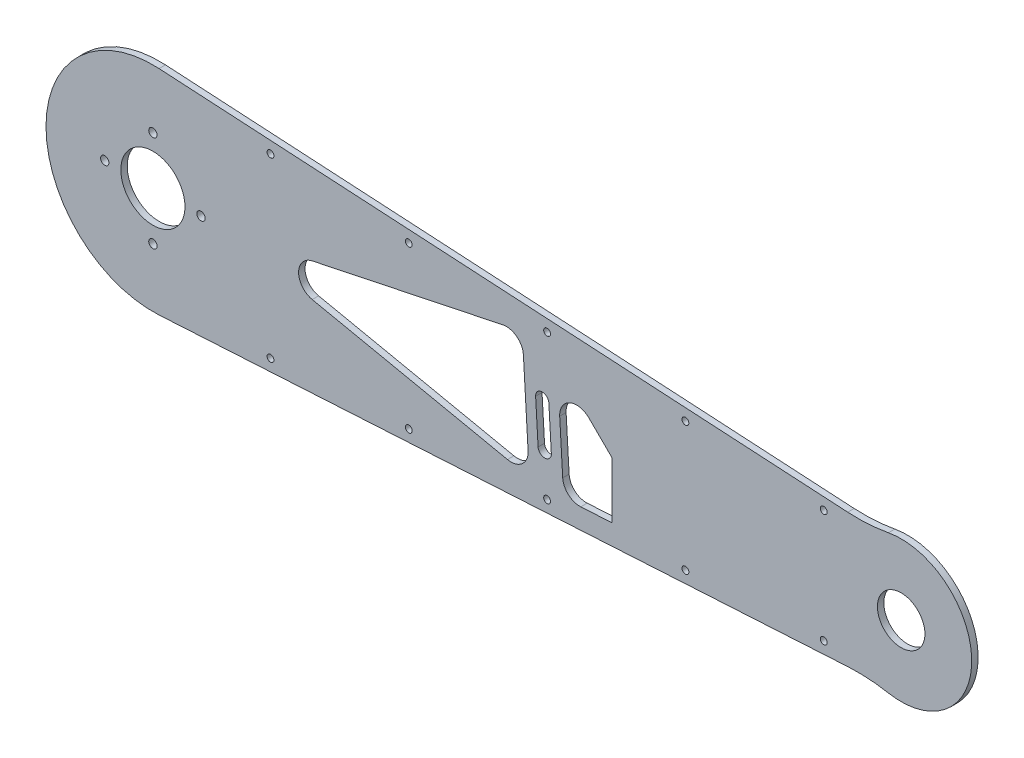
SolidWorks part; units mm, degrees
material "Thornel VCB-20 Carbon Cloth"
ref_plane "Front Plane" through (0, 0, 0) normal (0, 0, 1) x (1, 0, 0)
ref_plane "Top Plane" through (0, 0, 0) normal (0, 1, 0) x (1, 0, 0)
ref_plane "Right Plane" through (0, 0, 0) normal (1, 0, 0) x (0, 0, -1)
sketch "Sketch1" plane through (0, 0, 0) normal (0, 0, 1) x (1, 0, 0)
  line L0 (-175, 0) -> (175, 0) construction
  line L1 (-172.1122, 49.9165) -> (176.7203, 29.7354)
  line L2 (-172.1122, -49.9165) -> (176.7203, -29.7354)
  line L3 (138.7798, 26.4212) -> (-120, 41.3925) construction
  line L4 (-55.3051, -37.6497) -> (9.3899, -33.9068) construction
  line L5 (-125, 0) -> (-125, 62.9978) construction
  circle A0 centre (175, 0) radius 11.1125
  arc A1 (176.7203, 29.7354) -> (176.7203, -29.7354) centre (175, 0) cw
  circle A3 centre (-175, 0) radius 22.5 construction
  circle A7 centre (-175, 0) radius 15
  circle A9 centre (-120, 41.3925) radius 1.6
  circle A10 centre (-55.3051, 37.6497) radius 1.6
  circle A11 centre (9.3899, 33.9068) radius 1.6
  circle A12 centre (74.0848, 30.164) radius 1.6
  circle A13 centre (138.7798, 26.4212) radius 1.6
  circle A15 centre (138.7798, -26.4212) radius 1.6
  circle A16 centre (74.0848, -30.164) radius 1.6
  circle A17 centre (9.3899, -33.9068) radius 1.6
  circle A18 centre (-55.3051, -37.6497) radius 1.6
  circle A19 centre (-120, -41.3925) radius 1.6
  arc A20 (-172.1122, 49.9165) -> (-172.1122, -49.9165) centre (-175, 0) ccw
  point P4 (0, 0)
  point P14 (139.694, 27.6404)
  point P18 (-175, 22.5)
  point P21 (-197.5, 0)
  point P22 (-175, -22.5)
  point P23 (-152.5, 0)
  dimension "D2" = 22.225
  dimension "D3" = 50
  dimension "D5" = 45
  dimension "D6" = 3.2
  dimension "D7" = 259.2125
  dimension "D8" = 5
  dimension "D10" = 30
  dimension "D16" = 5
  dimension "D1" = 350
  dimension "D12" = 5.5
extrude "Boss-Extrude1" add sketch "Sketch1" along normal blind 3
sketch "Sketch4" plane through (0, 0, 3) normal (0, 0, 1) x (1, 0, 0)
  point P10 (-197.5, 0)
  point P13 (-175, 22.5)
  point P16 (-152.5, 0)
  point P19 (-175, -22.5)
hole_wizard "M3.5 Clearance Hole1" positions "Sketch4" profile "Sketch6" hole size "M3.5" standard "ANSI Metric" end condition up to next
sketch "Sketch6" plane through (-197.5, 0, 3) normal (1, 0, 0) x (0, -1, 0)
  line L0 (0, 0) -> (0, 3)
  line L1 (0, 3) -> (1.95, 3)
  line L2 (1.95, 3) -> (1.95, 0)
  line L5 (1.95, 0) -> (0, 0)
  line L11 (0, -6.35) -> (0, 107.95) construction
  dimension "Thru Hole Dia." = 3.9
  dimension "Thru Hole Depth" = 3
sketch "Sketch7" plane through (0, 0, 3) normal (0, 0, 1) x (1, 0, 0)
  line L0 (74.0848, 30.164) -> (74.0848, -30.164) construction
  line L1 (74.0848, -30.164) -> (138.7798, 0) construction
  line L2 (138.7798, 0) -> (74.0848, 30.164) construction
  line L3 (138.7798, 0) -> (-152.5, 0) construction
  line L4 (138.7798, -26.4212) -> (138.7798, 26.4212) construction
  line L5 (51.1115, 37.5653) -> (116.1295, 7.2506)
  line L6 (116.1295, -7.2506) -> (51.1115, -37.5653)
  line L7 (39.7309, -30.3147) -> (39.7309, 30.3147)
  line L8 (9.3899, -33.9068) -> (5.1337, 39.6623) construction
  line L9 (9.3899, 33.9068) -> (74.0848, -30.164) construction
  line L10 (9.3899, 33.9068) -> (74.0848, 30.164) construction
  line L11 (9.3899, -33.9068) -> (74.0848, -30.164) construction
  line L12 (-152.5, 0) -> (-55.3051, 37.6497) construction
  line L13 (-55.3051, 37.6497) -> (9.3899, 33.9068) construction
  line L14 (9.3899, 33.9068) -> (-152.5, 0) construction
  line L15 (108.4388, -39.3749) -> (108.4388, 16.6193)
  line L16 (100.9008, 24.6059) -> (40.8535, 28.0799)
  line L17 (34.7621, 14.409) -> (94.8094, -45.0591)
  line L18 (28.8948, 8.9604) -> (52.1347, -14.0553)
  line L19 (46.9674, -27.7262) -> (25.1321, -28.9894)
  line L20 (16.6834, -21.4648) -> (15.2788, 2.8141)
  line L21 (176.7203, 29.7354) -> (-172.1122, 49.9165) construction
  line L22 (-172.1122, -49.9165) -> (176.7203, -29.7354) construction
  line L23 (0.495, -18.6704) -> (-1.6922, 19.1364)
  line L24 (-11.3188, 26.5044) -> (-100.4803, 7.8301)
  line L25 (-100.4803, -7.8301) -> (-9.1316, -26.9625)
  line L35 (-197.5, 0) -> (-55.3051, 37.6497) construction
  line L52 (-55.3051, -37.6497) -> (-175, -22.5) construction
  line L53 (-15.2485, -47.7595) -> (-52.7603, -43.0116) construction
  line L54 (-0.7123, -39.5195) -> (1.8957, -39.8496) construction
  line L55 (8.2696, -14.5426) -> (7.1145, 5.4241) construction
  line L56 (5.1748, -14.7216) -> (4.0196, 5.245)
  line L57 (11.3644, -14.3635) -> (10.2093, 5.6031)
  arc A0 (116.1295, 7.2506) -> (116.1295, -7.2506) centre (112.7489, 0) cw
  arc A1 (51.1115, -37.5653) -> (39.7309, -30.3147) centre (47.7309, -30.3147) cw
  arc A2 (51.1115, 37.5653) -> (39.7309, 30.3147) centre (47.7309, 30.3147) ccw
  arc A3 (108.4388, 16.6193) -> (100.9008, 24.6059) centre (100.4388, 16.6193) ccw
  arc A4 (40.8535, 28.0799) -> (34.7621, 14.409) centre (40.3915, 20.0932) ccw
  arc A5 (108.4388, -39.3749) -> (94.8094, -45.0591) centre (100.4388, -39.3749) cw
  arc A6 (52.1347, -14.0553) -> (46.9674, -27.7262) centre (46.5054, -19.7395) cw
  arc A7 (25.1321, -28.9894) -> (16.6834, -21.4648) centre (24.6701, -21.0028) cw
  arc A8 (28.8948, 8.9604) -> (15.2788, 2.8141) centre (23.2655, 3.2762) ccw
  arc A9 (0.495, -18.6704) -> (-9.1316, -26.9625) centre (-7.4916, -19.1324) cw
  arc A10 (-1.6922, 19.1364) -> (-11.3188, 26.5044) centre (-9.6789, 18.6743) ccw
  arc A11 (-100.4803, 7.8301) -> (-100.4803, -7.8301) centre (-98.8404, 0) ccw
  circle A30 centre (-175, 0) radius 15 construction
  circle A31 centre (-175, 0) radius 15 construction
  circle A32 centre (-175, 0) radius 22.5 construction
  circle A49 centre (9.3899, -33.9068) radius 1.6 construction
  circle A50 centre (9.3899, -33.9068) radius 1.6
  arc A56 (5.1748, -14.7216) -> (11.3644, -14.3635) centre (8.2696, -14.5426) ccw
  arc A57 (10.2093, 5.6031) -> (4.0196, 5.245) centre (7.1145, 5.4241) ccw
  point P36 (131.6804, 0)
  point P59 (-137.8656, 0)
  point P102 (-15.2485, -47.7595)
  point P126 (7.692, -4.5593)
  dimension "D8" = 8
  dimension "D12" = 5
  dimension "D20" = 3.1
  dimension "D1" = 3
  dimension "D3" = 8
  dimension "D4" = 8
  dimension "D5" = 8
  dimension "D6" = 16
  dimension "D7" = 6
  dimension "D14" = 5
  dimension "D16" = 24.8967
  dimension "D22" = 20
extrude "Cut-Extrude1" cut sketch "Sketch7" against normal blind 10 contours L57 A57 L56 A56 | L24 A11 L25 A9 L23 A10 | L18 A8 L20 A7 L19 A6 region at (27.3491, -10.0674, 3) region at (-42.7127, -0.2073, 3) region at (7.692, -4.5593, 3)
sketch "Sketch9" plane through (0, 0, 3) normal (0, 0, 1) x (1, 0, 0)
  line L2 (176.7203, 29.7354) -> (-172.1122, 49.9165) construction
  line L3 (-172.1122, -49.9165) -> (176.7203, -29.7354) construction
  line L4 (254.5375, 0) -> (208, 0) construction
  line L5 (200.557, 2) -> (203.931, 2)
  line L6 (200.557, -2) -> (203.931, -2)
  line L7 (162.9445, 26.3755) -> (155.7345, 26.7926)
  line L8 (162.9445, -26.3755) -> (155.7345, -26.7926)
  arc A1 (155.7345, -26.7926) -> (155.7345, 26.7926) centre (175, 0) ccw
  arc A2 (176.7203, -29.7354) -> (176.7203, 29.7354) centre (175, 0) ccw construction
  arc A3 (200.557, -2) -> (200.557, 2) centre (175, 0) ccw
  arc A4 (162.9445, 26.3755) -> (203.931, 2) centre (175, 0) cw
  arc A5 (203.931, -2) -> (162.9445, -26.3755) centre (175, 0) cw
  dimension "D1" = 33
  dimension "D2" = 4
  dimension "D3" = 4
extrude "Boss-Extrude2" add sketch "Sketch9" against normal up to surface (3 mm away) up to face at (-37.5386, -0.0271, 0)
fillet "Fillet1" radius 1 rebuild error yes
fillet "Fillet2" radius 80 2 edges at (162.5368, 30.556, 1.5) (162.5368, -30.556, 1.5)
